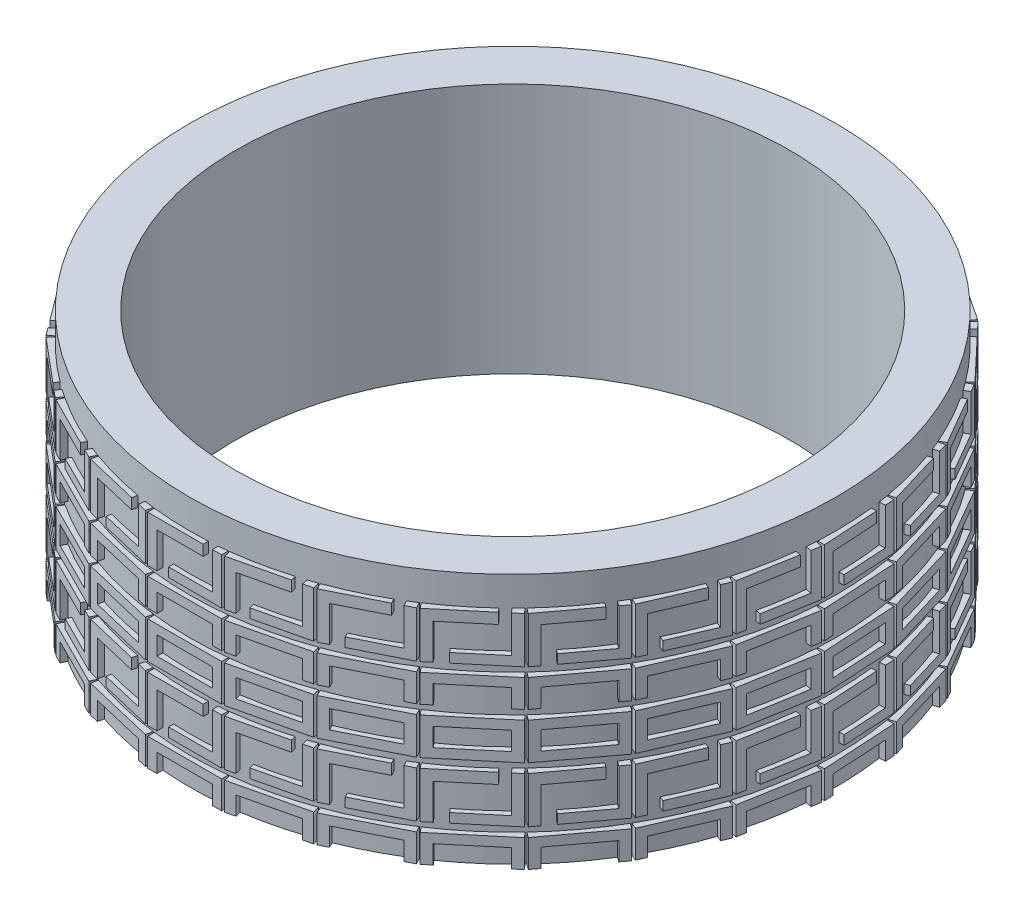
SolidWorks part; units mm, degrees
ref_plane "Alzado" through (0, 0, 0) normal (0, 0, 1) x (1, 0, 0)
ref_plane "Planta" through (0, 0, 0) normal (0, 1, 0) x (1, 0, 0)
ref_plane "Vista lateral" through (0, 0, 0) normal (1, 0, 0) x (0, 0, -1)
sketch "Croquis1" plane through (0, 0, 0) normal (0, 1, 0) x (1, 0, 0)
  circle A0 centre (0, 0) radius 35
  circle A1 centre (0, 0) radius 30
  dimension "D1" = 70
  dimension "D2" = 60
extrude "Saliente-Extruir1" add sketch "Croquis1" along normal blind 27.1642
ref_plane "Plano1" through (0, 0, 35) normal (0, 0, 1) x (1, 0, 0)
sketch "Croquis2" plane through (0, 0, 35) normal (0, 0, 1) x (1, 0, 0)
  line L0 (-4, 0) -> (-4, 3)
  line L1 (-35, 0) -> (35, 0) construction
  line L2 (-4, 3) -> (4, 3)
  line L3 (4, 3) -> (4, 0)
  line L4 (4, 0) -> (3, 0)
  line L5 (3, 0) -> (3, 2)
  line L6 (3, 2) -> (-3, 2)
  line L7 (-3, 2) -> (-3, 0)
  line L8 (-3, 0) -> (-4, 0)
  line L9 (0.1402, 4) -> (4, 4)
  line L10 (4, 4) -> (4, 9)
  line L11 (4, 9) -> (3, 9)
  line L12 (3, 9) -> (3, 5)
  line L13 (3, 5) -> (-1.7433, 5)
  line L14 (-1.7433, 5) -> (-1.7433, 4)
  line L15 (-1.7433, 4) -> (0.1402, 4)
  line L16 (-3, 4) -> (-3, 7.8512)
  line L17 (-3, 7.8512) -> (2, 7.8512)
  line L18 (2, 7.8512) -> (2, 9)
  line L19 (2, 9) -> (-4, 9)
  line L20 (-4, 9) -> (-4, 4)
  line L21 (-4, 4) -> (-3, 4)
  point P23 (4, 1.5)
  dimension "D1" = 3
  dimension "D2" = 5
  dimension "D3" = 1
  dimension "D4" = 1
  dimension "D5" = 5
  dimension "D6" = 6
  dimension "D7" = 8
  dimension "D8" = 4
  dimension "D9" = 1
  dimension "D10" = 1
  dimension "D11" = 1
  dimension "D12" = 1
  dimension "D13" = 1
  dimension "D14" = 1
  dimension "D15" = 1
extrude "Saliente-Extruir2" add sketch "Croquis2" along normal blind 0.5 and the other way blind 0.5
pattern_linear "MatrizL1" count 2 spacing 15 along (0, 1, 0) of "Saliente-Extruir2"
sketch "Croquis3" plane through (0, 0, 35) normal (0, 0, 1) x (1, 0, 0)
  line L0 (-4, 15) -> (-3, 15) construction
  line L1 (-4, 14) -> (4, 14)
  line L2 (-4, 14) -> (-4, 10)
  line L3 (-4, 10) -> (4, 10)
  line L4 (4, 14) -> (4, 10)
  line L5 (3, 11) -> (-3, 11)
  line L6 (3, 11) -> (3, 13)
  line L7 (3, 13) -> (-3, 13)
  line L8 (-3, 11) -> (-3, 13)
  line L9 (2, 9) -> (-4, 9) construction
  dimension "D1" = 1
  dimension "D2" = 1
  dimension "D3" = 4
  dimension "D4" = 4
  dimension "D5" = 1
  dimension "D6" = 1
  dimension "D7" = 1
  dimension "D8" = 1
extrude "Saliente-Extruir3" add sketch "Croquis3" along normal blind 0.5 and the other way blind 0.5
pattern_circular "MatrizC1" count 27 over 360 about axis through (0, 0, 0) along (0, 1, 0) of "Saliente-Extruir3", "MatrizL1", "Saliente-Extruir2"
scale "Scale1" scale about centroid uniform scaling yes scale factor 0.957143
